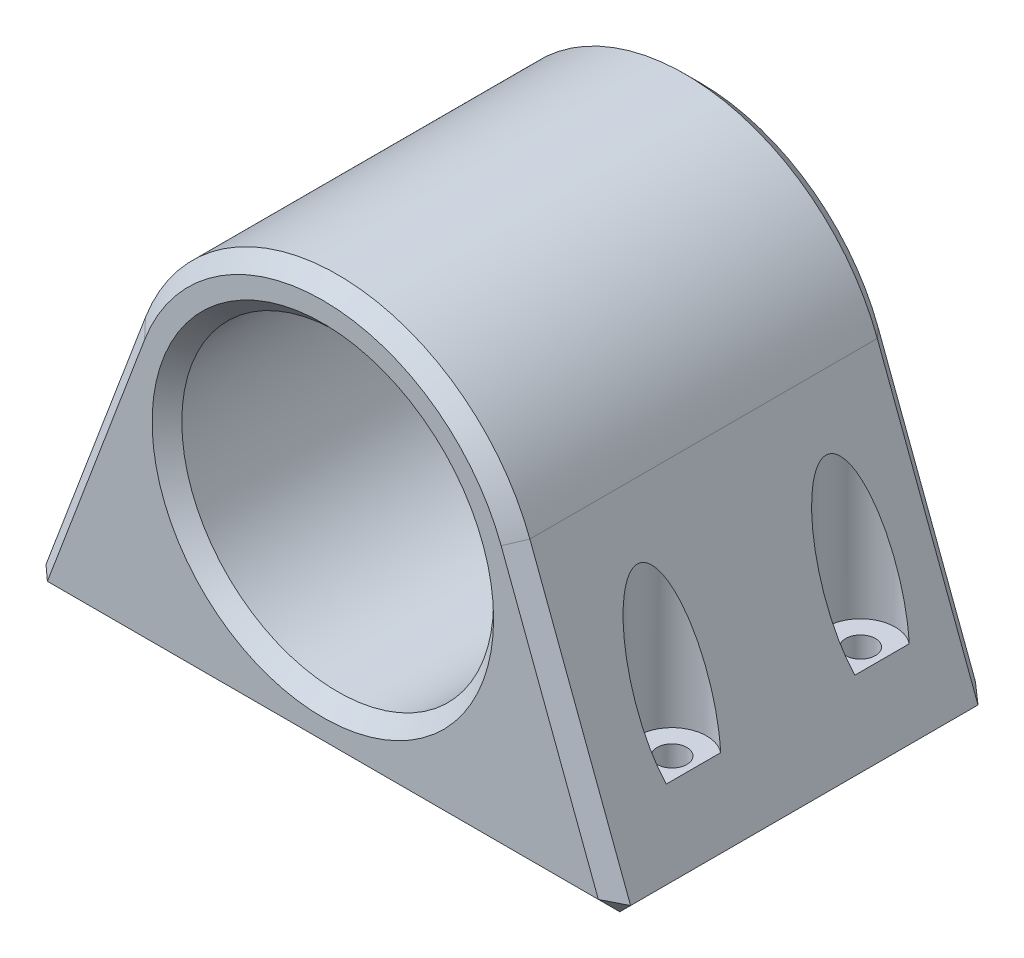
SolidWorks part; units mm, degrees
ref_plane "Front Plane" through (0, 0, 0) normal (0, 0, 1) x (1, 0, 0)
ref_plane "Top Plane" through (0, 0, 0) normal (0, 1, 0) x (1, 0, 0)
ref_plane "Right Plane" through (0, 0, 0) normal (1, 0, 0) x (0, 0, -1)
sketch "Sketch1" plane through (0, 0, 0) normal (0, 0, 1) x (1, 0, 0)
  line L3 (255, -0.5) -> (315, -0.5)
  line L7 (255, -0.5) -> (195, -0.5)
  line L10 (195, -0.5) -> (216.1687, 55.6417)
  line L11 (315, -0.5) -> (293.8313, 55.6417)
  arc A0 (293.8313, 55.6417) -> (216.1687, 55.6417) centre (255, 41) ccw
  circle A2 centre (255, 41) radius 31.5
  circle A8 centre (255, 41) radius 41.5 construction
  point P3 (210, 0)
  point P4 (300, 0)
  point P5 (210, 8)
  point P6 (300, 8)
  point P9 (150, -74)
  point P11 (255, 41)
  point P13 (294.6866, 53.1334)
  point P15 (296.5, 41)
  point P23 (175, -74)
  dimension "D1" = 10
extrude "Boss-Extrude1" add sketch "Sketch1" along normal blind 76.2
sketch "Sketch2" plane through (0, -0.5, 0) normal (0, -1, 0) x (1, 0, 0)
  circle A0 centre (205, 55.65) radius 3
  circle A1 centre (205, 17.55) radius 3
  circle A2 centre (305, 17.55) radius 3
  circle A3 centre (305, 55.65) radius 3
extrude "Cut-Extrude1" cut sketch "Sketch2" against normal through all
sketch3d "3DSketch2" plane through (0, 0, 0) normal (0, 0, 1) x (1, 0, 0)
  dimension "D1" = 15
sketch "Sketch3" plane through (0, 14.5, 0) normal (0, -1, 0) x (-1, 0, 0)
  circle A0 centre (-205, -55.65) radius 7
  circle A9 centre (-205, -17.55) radius 7
  circle A10 centre (-305, -17.55) radius 7
  circle A11 centre (-305, -55.65) radius 7
extrude "Cut-Extrude2" cut sketch "Sketch3" against normal through all
chamfer "Chamfer1" distance 3 angle 45 16 edges at (286.5, 41, 76.2) (255, 82.5, 76.2) (255, -0.5, 76.2) (205.5843, 27.5708, 76.2) (304.4157, 27.5708, 76.2) (255, 82.5, 0) (205.5843, 27.5708, 0) (255, -0.5, 0) (304.4157, 27.5708, 0) (286.5, 41, 0) (302, -0.5, 55.65) (302, -0.5, 17.55) (208, -0.5, 17.55) (208, -0.5, 55.65) (315, -0.5, 38.1) (195, -0.5, 38.1)
